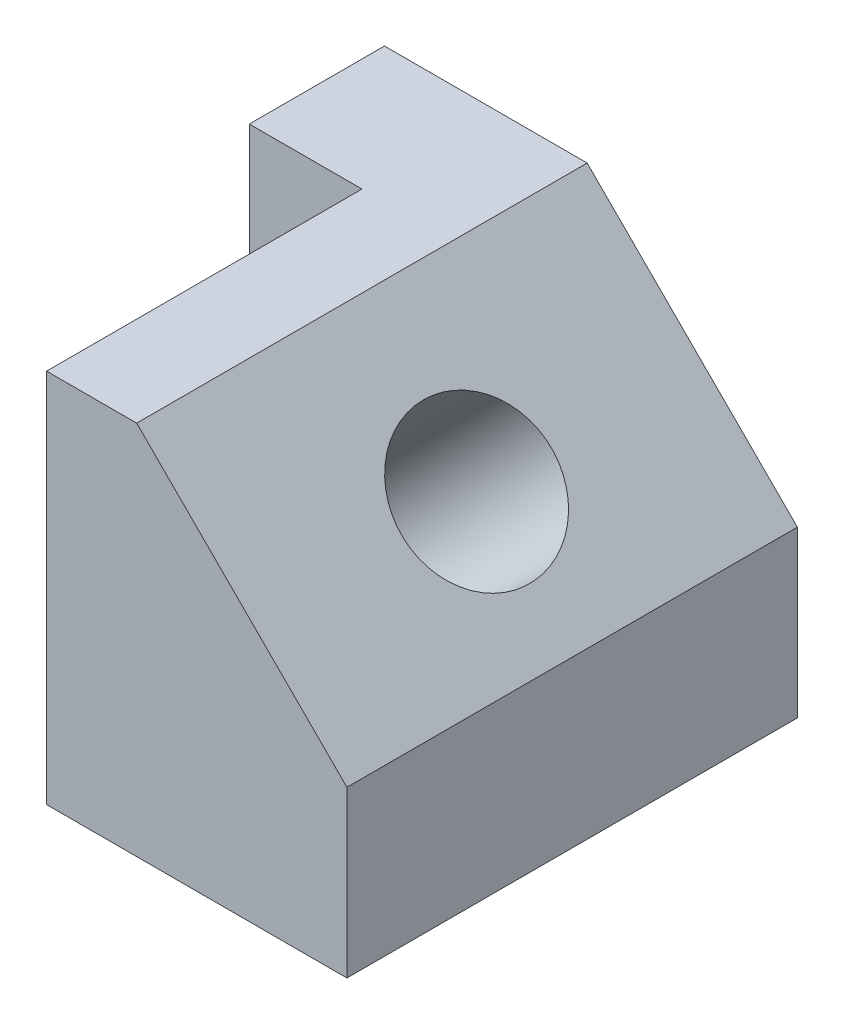
SolidWorks part; units mm, degrees
ref_plane "Front Plane" through (0, 0, 0) normal (0, 0, 1) x (1, 0, 0)
ref_plane "Top Plane" through (0, 0, 0) normal (0, 1, 0) x (1, 0, 0)
ref_plane "Right Plane" through (0, 0, 0) normal (1, 0, 0) x (0, 0, -1)
sketch "Sketch1" plane through (0, 0, 0) normal (0, 0, 1) x (1, 0, 0)
  line L0 (-40, 50) -> (-40, 0)
  line L1 (-40, 0) -> (0, 0)
  line L2 (0, 0) -> (0, 22)
  line L3 (0, 22) -> (-28, 50)
  line L4 (-28, 50) -> (-40, 50)
  line L6 (-40, 50) -> (-55, 50)
  line L7 (-40, 50) -> (-40, 0)
  line L8 (-40, 0) -> (-55, 0)
  line L9 (-55, 50) -> (-55, 0)
  point P1 (0, 0)
  point P8 (-30.6395, 85.381)
  point P9 (0, 0)
  dimension "D1" = 22
  dimension "D2" = 50
  dimension "D3" = 45
  dimension "D4" = 15
  dimension "D5" = 40
extrude "Boss-Extrude1" add sketch "Sketch1" along normal blind 18 contours L6 L9 L8 L0 region at (-47.5, 25, 0)
extrude "Boss-Extrude2" add sketch "Sketch1<3>" along normal blind 60 contours L3 L4 L0 L1 L2 region at (-22.6003, 21.1808, 0)
sketch "Sketch1<3>" plane through (0, 0, 0) normal (0, 0, 1) x (1, 0, 0) same geometry as "Sketch1"
sketch "Sketch2" plane through (11, 11, 0) normal (0.7071, 0.7071, 0) x (0, 0, -1)
  line L0 (0, 15.5563) -> (0, 55.1543) construction
  line L1 (-60, 15.5563) -> (0, 15.5563) construction
  circle A0 centre (-30, 33.5563) radius 10
  dimension "D1" = 20
  dimension "D2" = 30
  dimension "D3" = 18
extrude "Cut-Extrude2" cut sketch "Sketch2" against normal blind 60
